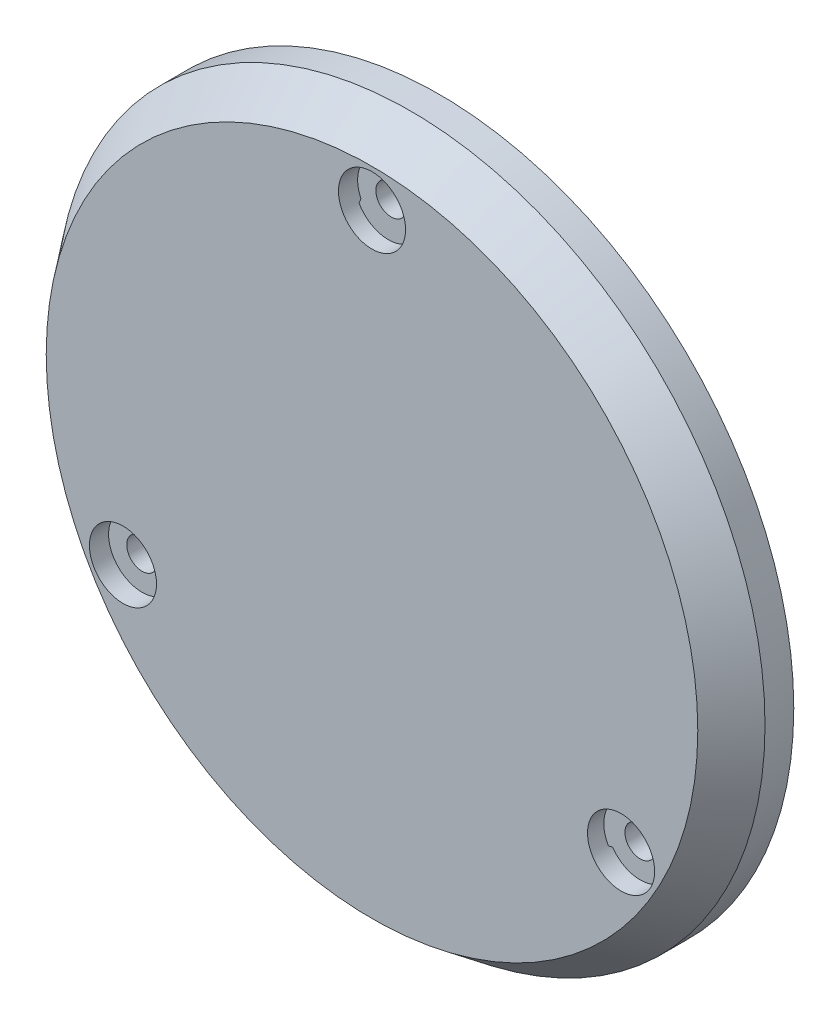
SolidWorks part; units mm, degrees
ref_plane "Спереди" through (0, 0, 0) normal (0, 0, 1) x (1, 0, 0)
ref_plane "Сверху" through (0, 0, 0) normal (0, 1, 0) x (1, 0, 0)
ref_plane "Справа" through (0, 0, 0) normal (1, 0, 0) x (0, 0, -1)
other "Configuration Table"
sketch "Эскиз1" plane through (0, 0, 0) normal (0, 0, 1) x (1, 0, 0)
  circle A0 centre (0, 0) radius 37
  dimension "D1" = 74
extrude "Бобышка-Вытянуть1" add sketch "Эскиз1" along normal blind 4 draft 37
sketch "Эскиз2" plane through (0, 0, 0) normal (0, 0, -1) x (-1, 0, 0)
  circle A0 centre (0, 0) radius 35
  circle A1 centre (0, 0) radius 30
  dimension "D1" = 60
extrude "Бобышка-Вытянуть2" add sketch "Эскиз2" along normal blind 2
sketch "Эскиз3" plane through (0, 0, -2) normal (0, 0, -1) x (-1, 0, 0)
  circle A0 centre (0, 0) radius 35
  circle A1 centre (0, 0) radius 32.9
  dimension "D1" = 65.8
extrude "Вырез-Вытянуть1" cut sketch "Эскиз3" against normal blind 2
sketch "Эскиз4" plane through (0, 0, 0) normal (0, 0, -1) x (-1, 0, 0)
  circle A0 centre (0, 0) radius 30
extrude "Вырез-Вытянуть2" cut sketch "Эскиз4" against normal blind 2.3 draft 34
sketch "Эскиз5" plane through (0, 0, -2) normal (0, 0, -1) x (-1, 0, 0)
  circle A0 centre (0, 30) radius 1.6
  circle A1 centre (25.9808, -15) radius 1.6
  circle A2 centre (-25.9808, -15) radius 1.6
  point P12 (0, 0)
  dimension "D1" = 3.2
  dimension "D2" = 30
  dimension "D3" = 3
extrude "Вырез-Вытянуть3" cut sketch "Эскиз5" against normal through all
sketch "Эскиз6" plane through (0, 0, -2) normal (0, 0, -1) x (-1, 0, 0)
  arc A0 (-3.8655, 28.9714) -> (3.8655, 28.9714) centre (0, 30) ccw
  arc A15 (-3.8655, 28.9714) -> (-7.4644, 31.1172) centre (-6.7646, 28.2) ccw
  arc A16 (3.8655, 28.9714) -> (7.4644, 31.1172) centre (6.7646, 28.2) cw
  arc A18 (-7.4644, 31.1172) -> (-30.6805, -9.0943) centre (0, 0) ccw
  arc A19 (27.0227, -11.1381) -> (30.6805, -9.0943) centre (27.8042, -8.2417) ccw
  arc A20 (27.0227, -11.1381) -> (23.1572, -17.8333) centre (25.9808, -15) ccw
  arc A21 (23.1572, -17.8333) -> (23.2161, -22.023) centre (21.0396, -19.9583) cw
  arc A22 (-23.1572, -17.8333) -> (-23.2161, -22.023) centre (-21.0396, -19.9583) ccw
  arc A23 (-23.1572, -17.8333) -> (-27.0227, -11.1381) centre (-25.9808, -15) ccw
  arc A24 (-27.0227, -11.1381) -> (-30.6805, -9.0943) centre (-27.8042, -8.2417) cw
  arc A25 (30.6805, -9.0943) -> (7.4644, 31.1172) centre (0, 0) ccw
  arc A26 (-23.2161, -22.023) -> (23.2161, -22.023) centre (0, 0) ccw
  circle A27 centre (0, 0) radius 48.2986
  point P12 (0, 0)
  point P20 (-31.8, -3.5721)
  point P25 (0, 0)
  point P27 (31.8, 3.5721)
  dimension "D1" = 8
  dimension "D4" = 3
  dimension "D2" = 3
extrude "Вырез-Вытянуть4" cut sketch "Эскиз6" against normal blind 2
sketch "Эскиз7" plane through (0, 0, 0) normal (0, 0, -1) x (-1, 0, 0)
  arc A0 (-4.0607, 32.0333) -> (4.0607, 32.0333) centre (0, 30) ccw
  circle A1 centre (0, 30) radius 1.6
  circle A2 centre (25.9808, -15) radius 1.6
  arc A3 (29.772, -12.5) -> (25.7114, -19.5333) centre (25.9808, -15) ccw
  circle A4 centre (-25.9808, -15) radius 1.6
  arc A5 (-25.7114, -19.5333) -> (-29.772, -12.5) centre (-25.9808, -15) ccw
  arc A6 (-29.772, -12.5) -> (-25.7114, -19.5333) centre (0, 0) ccw
  arc A7 (4.0607, 32.0333) -> (-4.0607, 32.0333) centre (0, 0) ccw
  arc A8 (25.7114, -19.5333) -> (29.772, -12.5) centre (0, 0) ccw
  point P14 (0, 0)
  dimension "D1" = 3
extrude "Бобышка-Вытянуть3" add sketch "Эскиз7" against normal blind 2
sketch "Эскиз8" plane through (0, 0, 4) normal (0, 0, 1) x (1, 0, 0)
  circle A0 centre (-25.9808, -15) radius 3.5
  circle A1 centre (0, 30) radius 3.5
  circle A2 centre (25.9808, -15) radius 3.5
  point P10 (0, 0)
  dimension "D1" = 7
  dimension "D2" = 3
extrude "Вырез-Вытянуть5" cut sketch "Эскиз8" against normal blind 2
fillet "Скругление1" [suppressed] radius 0.5
sketch "Эскиз9" plane through (0, 0, 0) normal (0, 0, -1) x (-1, 0, 0)
  circle A0 centre (0, 0) radius 37
  circle A1 centre (0, 0) radius 35.75
  dimension "D1" = 71.5
extrude "Бобышка-Вытянуть4" add sketch "Эскиз9" along normal blind 3
fillet "Скругление2" radius 1 6 edges at (-23.6426, -18.4669, -1) (-27.8141, -11.2417, -1) (-4.1715, 29.7086, -1) (4.1715, 29.7086, -1) (23.6426, -18.4669, -1) (27.8141, -11.2417, -1)
chamfer "Фаска1" distance 0.4 angle 45 12 edges at (23.1788, -20.6093, -2) (0, -30, -2) (-23.1788, -20.6093, -2) (0, -32, -2) (29.4376, -9.7688, -2) (27.7128, 16, -2) (6.2587, 30.3781, -2) (25.9808, 15, -2) (-6.2587, 30.3781, -2) (-27.7128, 16, -2) (-29.4376, -9.7688, -2) (-25.9808, 15, -2)
chamfer "Фаска2" distance 0.4 angle 45 1 edges at (-35.75, 0, -3)
equation "\"65б8\"=66.2"
